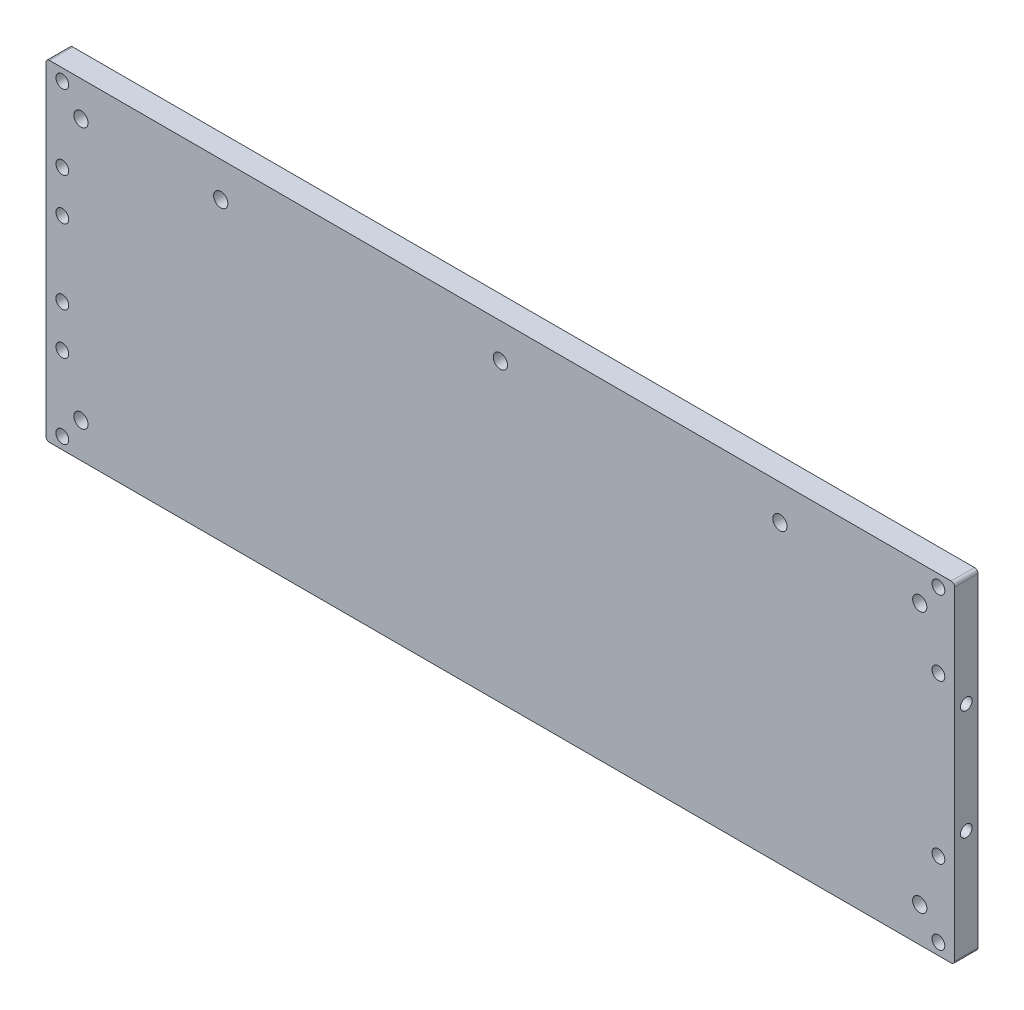
SolidWorks part; units mm, degrees
ref_plane "Front Plane" through (0, 0, 0) normal (0, 0, 1) x (1, 0, 0)
ref_plane "Top Plane" through (0, 0, 0) normal (0, 1, 0) x (1, 0, 0)
ref_plane "Right Plane" through (0, 0, 0) normal (1, 0, 0) x (0, 0, -1)
sketch "Sketch1" plane through (0, 0, 0) normal (0, 0, 1) x (1, 0, 0)
  line L1 (195, -71) -> (-195, -71)
  line L2 (195, -71) -> (195, 71)
  line L3 (195, 71) -> (-195, 71)
  line L4 (-195, -71) -> (-195, 71)
  line L5 (195, -71) -> (-195, 71) construction
  line L6 (195, 71) -> (-195, -71) construction
  point P0 (0, 0)
  dimension "D1" = 390
  dimension "D2" = 142
extrude "Boss-Extrude1" add sketch "Sketch1" along normal mid plane 10
sketch "Sketch2" plane through (0, 0, -5) normal (0, 0, -1) x (-1, 0, 0)
  line L0 (-188, 71) -> (-188, -71) construction
  line L1 (-195, 71) -> (195, 71) construction
  line L2 (195, -71) -> (-195, -71) construction
  line L3 (-195, -71) -> (-195, 71) construction
  line L4 (188, 71) -> (188, -71) construction
  line L5 (195, 71) -> (195, -71) construction
  line L6 (-195, 66) -> (195, 66) construction
  line L7 (-195, -66) -> (195, -66) construction
  line L8 (-195, 34) -> (195, 34) construction
  line L9 (-195, -34) -> (195, -34) construction
  circle A0 centre (-188, 66) radius 2.75
  circle A1 centre (-188, -66) radius 2.75
  circle A2 centre (188, 66) radius 2.75
  circle A3 centre (188, -66) radius 2.75
  circle A4 centre (-188, 34) radius 2.75
  circle A5 centre (-188, -34) radius 2.75
  circle A6 centre (188, 34) radius 2.75
  circle A7 centre (188, -34) radius 2.75
  dimension "D5" = 5.5
  dimension "D6" = 5.5
  dimension "D7" = 5.5
  dimension "D8" = 5.5
  dimension "D11" = 5.5
  dimension "D12" = 5.5
  dimension "D13" = 5.5
  dimension "D14" = 5.5
  dimension "D1" = 7
  dimension "D2" = 7
  dimension "D3" = 5
  dimension "D4" = 5
  dimension "D9" = 32
  dimension "D10" = 32
extrude "Cut-Extrude1" cut sketch "Sketch2" against normal through all
sketch "Sketch3" plane through (0, 0, 5) normal (0, 0, 1) x (1, 0, 0)
  line L0 (-195, 56) -> (195, 56) construction
  line L1 (-195, 71) -> (-195, -71) construction
  line L2 (195, -71) -> (195, 71) construction
  line L3 (-195, -56) -> (195, -56) construction
  line L4 (-180, 71) -> (-180, -71) construction
  line L5 (195, 71) -> (-195, 71) construction
  line L6 (-195, -71) -> (195, -71) construction
  line L7 (180, 71) -> (180, -71) construction
  line L8 (-120, 71) -> (-120, -71) construction
  line L9 (120, 71) -> (120, -71) construction
  circle A0 centre (-180, 56) radius 3.05
  circle A1 centre (180, 56) radius 3.05
  circle A2 centre (180, -56) radius 3.05
  circle A3 centre (-180, -56) radius 3.05
  circle A4 centre (0, 56) radius 3.05
  circle A5 centre (-120, 56) radius 3.05
  circle A6 centre (120, 56) radius 3.05
  dimension "D5" = 6.1
  dimension "D6" = 6.1
  dimension "D7" = 6.1
  dimension "D8" = 6.1
  dimension "D9" = 6.1
  dimension "D12" = 6.1
  dimension "D13" = 6.1
  dimension "D1" = 15
  dimension "D2" = 15
  dimension "D3" = 15
  dimension "D4" = 15
  dimension "D10" = 75
  dimension "D11" = 75
extrude "Cut-Extrude2" cut sketch "Sketch3" against normal through all
sketch "Sketch4" plane through (0, 0, 5) normal (0, 0, 1) x (1, 0, 0)
  circle A0 centre (-180, 56) radius 5
  circle A1 centre (-180, -56) radius 5
  circle A2 centre (180, 56) radius 5
  circle A3 centre (180, -56) radius 5
  dimension "D1" = 10
  dimension "D2" = 10
  dimension "D3" = 10
  dimension "D4" = 10
extrude "Cut-Extrude3" [suppressed] cut sketch "Sketch4" against normal blind 3.5
sketch "Sketch5" plane through (195, 0, 0) normal (1, 0, 0) x (0, 0, -1)
  line L0 (0, 71) -> (0, -71) construction
  line L1 (-5, 71) -> (5, 71) construction
  line L2 (-5, -71) -> (5, -71) construction
  circle A0 centre (0, 23.6) radius 2.5
  circle A1 centre (0, -23.6) radius 2.5
  dimension "D1" = 5
  dimension "D2" = 5
  dimension "D3" = 23.6
  dimension "D4" = 23.6
extrude "Cut-Extrude4" cut sketch "Sketch5" against normal blind 10
sketch "Sketch6" plane through (0, 0, 5) normal (0, 0, 1) x (1, 0, 0)
  line L0 (-188, 34) -> (-188, -34) construction
  line L1 (-188, 0) -> (195, 0) construction
  line L2 (195, -71) -> (195, 71) construction
  circle A0 centre (-188, 16) radius 2.75
  circle A1 centre (-188, -16) radius 2.75
  circle A2 centre (-188, 34) radius 2.75 construction
  dimension "D1" = 16
  dimension "D3" = 5.5
  dimension "D4" = 5.5
  dimension "D2" = 16
extrude "Cut-Extrude5" cut sketch "Sketch6" against normal through all
fillet "Fillet1" radius 1.5 4 edges at (-195, -71, 0) (195, -71, 0) (195, 71, 0) (-195, 71, 0)
equation "\"D3@Sketch5\"=47.2/2"
equation "\"D4@Sketch5\"=47.2/2"
equation "\"D1@Sketch6\"=32/2"
equation "\"D2@Sketch6\"=32/2"
equation "\"D6@Sketch3\"=6.1"
equation "\"D13@Sketch3\"=\"D6@Sketch3\""
equation "\"D9@Sketch3\"=\"D6@Sketch3\""
equation "\"D12@Sketch3\"=\"D6@Sketch3\""
equation "\"D7@Sketch3\"=\"D6@Sketch3\""
equation "\"D5@Sketch3\"=\"D6@Sketch3\""
equation "\"D8@Sketch3\"=\"D6@Sketch3\""
